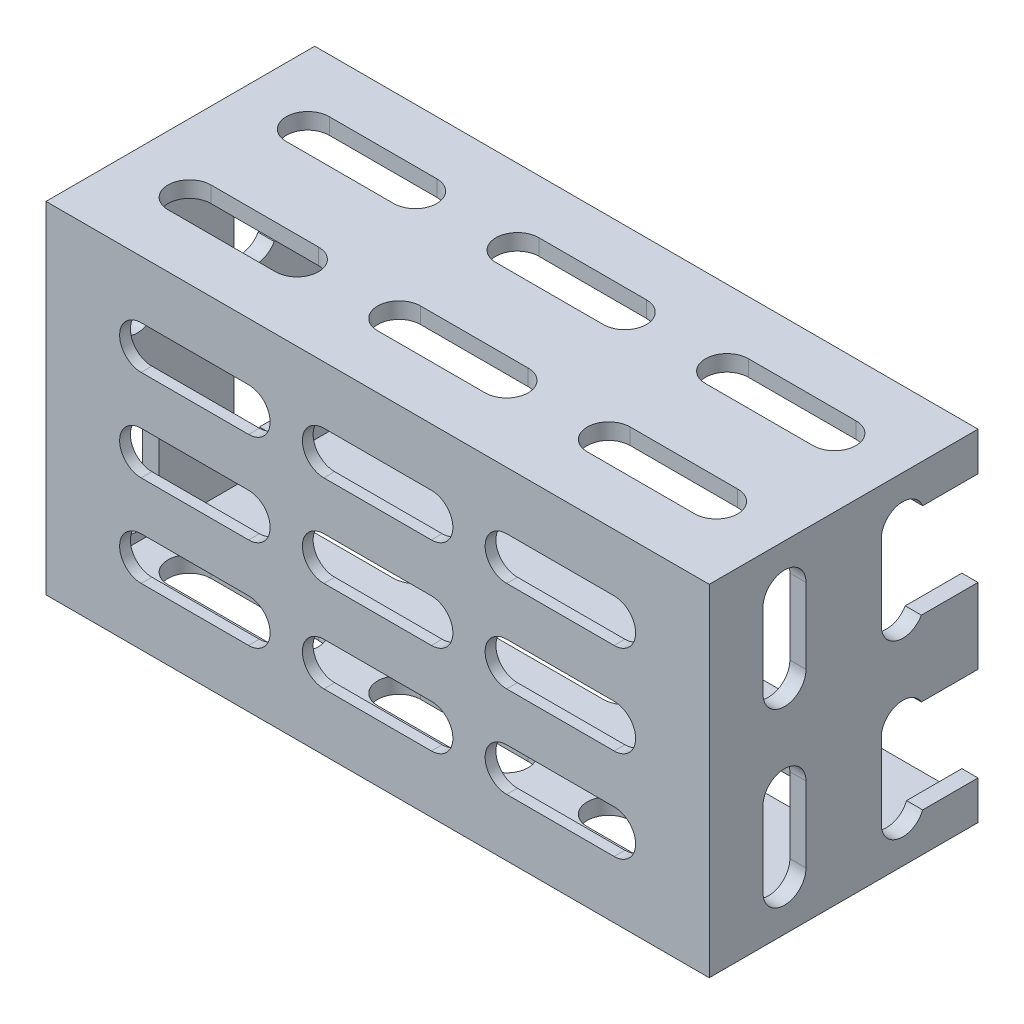
SolidWorks part; units mm, degrees
ref_plane "Front Plane" through (0, 0, 0) normal (0, 0, 1) x (1, 0, 0)
ref_plane "Top Plane" through (0, 0, 0) normal (0, 1, 0) x (1, 0, 0)
ref_plane "Right Plane" through (0, 0, 0) normal (1, 0, 0) x (0, 0, -1)
sketch "Sketch1" plane through (0, 0, 0) normal (0, 0, 1) x (1, 0, 0)
  line L4 (29.35, -14.35) -> (-29.35, -14.35)
  line L5 (29.25, -14.25) -> (-29.25, -14.25) construction
  line L6 (29.25, -14.25) -> (29.25, 14.25) construction
  line L7 (29.25, 14.25) -> (-29.25, 14.25) construction
  line L16 (-29.25, -14.25) -> (-29.25, 14.25) construction
  line L17 (-29.35, -14.35) -> (-29.35, 14.35)
  line L18 (29.35, 14.35) -> (-29.35, 14.35)
  line L19 (29.35, -14.35) -> (29.35, 14.35)
  line L20 (-30.85, -15.85) -> (-30.85, 15.85)
  line L21 (30.85, 15.85) -> (-30.85, 15.85)
  line L22 (30.85, -15.85) -> (30.85, 15.85)
  line L23 (30.85, -15.85) -> (-30.85, -15.85)
  dimension "D1" = 0.1
  dimension "D2" = 1.5
extrude "Boss-Extrude1" add sketch "Sketch1" along normal blind 19
sketch "Sketch2" plane through (0, 0, 19) normal (0, 0, 1) x (1, 0, 0)
  line L4 (-30.85, -15.85) -> (30.85, -15.85)
  line L5 (-30.85, -15.85) -> (30.85, -15.85)
  line L6 (-30.85, 15.85) -> (-30.85, -15.85)
  line L7 (30.85, 15.85) -> (-30.85, 15.85)
  line L10 (-30.85, 15.85) -> (-30.85, -15.85)
  line L11 (30.85, 15.85) -> (-30.85, 15.85)
  line L12 (30.85, -15.85) -> (30.85, 15.85)
  line L13 (30.85, -15.85) -> (30.85, 15.85)
  dimension "D1" = 0
extrude "Boss-Extrude2" add sketch "Sketch2" along normal blind 1
sketch "Sketch3" plane through (0, 0, 0) normal (0, 0, -1) x (-1, 0, 0)
  line L1 (29.35, -14.35) -> (-29.35, -14.35) construction
  line L4 (-30.85, -15.85) -> (30.85, -15.85)
  line L5 (30.85, 15.85) -> (-30.85, 15.85)
  line L6 (30.85, -15.85) -> (30.85, 15.85)
  line L7 (-30.85, -15.85) -> (30.85, -15.85)
  line L9 (30.85, 15.85) -> (9, 15.85)
  line L10 (30.85, -15.85) -> (30.85, 15.85)
  line L14 (29.35, 14.35) -> (29.35, -14.35) construction
  line L20 (-29.35, 14.35) -> (29.35, 14.35) construction
  line L21 (-29.35, -14.35) -> (-29.35, 14.35) construction
  line L22 (29.35, -14.35) -> (-29.35, -14.35)
  line L23 (29.35, 14.35) -> (29.35, -14.35)
  line L24 (-30.85, 15.85) -> (-30.85, -15.85)
  line L25 (-30.85, 15.85) -> (-30.85, -15.85)
  line L26 (-29.35, 14.35) -> (-9, 14.35)
  line L27 (-29.35, -14.35) -> (-29.35, 14.35)
  line L30 (-9, 15.85) -> (-30.85, 15.85)
  line L31 (9, 14.35) -> (29.35, 14.35)
  line L32 (-9, 15.85) -> (9, 15.85)
  line L33 (9, 14.35) -> (-9, 14.35)
  dimension "D1" = 0
extrude "Boss-Extrude3" add sketch "Sketch3" along normal up to surface (5 mm away)
sketch "Sketch8" plane through (0, 0, 19) normal (0, 0, -1) x (-1, 0, 0)
  line L0 (12, 6.5) -> (22, 6.5) construction
  line L1 (12, -2) -> (22, -2) construction
  line L2 (12, -10.5) -> (22, -10.5) construction
  line L3 (-5, -10.5) -> (5, -10.5) construction
  line L4 (-22, -10.5) -> (-12, -10.5) construction
  line L5 (-22, -2) -> (-12, -2) construction
  line L6 (-5, 6.5) -> (5, 6.5) construction
  line L7 (-22, 6.5) -> (-12, 6.5) construction
  line L8 (12, 6.5) -> (22, 6.5)
  line L9 (12, -2) -> (22, -2)
  line L10 (12, -10.5) -> (22, -10.5)
  line L11 (-5, -10.5) -> (5, -10.5)
  line L12 (-22, -10.5) -> (-12, -10.5)
  line L13 (-22, -2) -> (-12, -2)
  line L14 (-5, 6.5) -> (5, 6.5)
  line L15 (-22, 6.5) -> (-12, 6.5)
  line L16 (22, -6.5) -> (12, -6.5) construction
  line L17 (5, -6.5) -> (-5, -6.5) construction
  line L18 (-12, -6.5) -> (-22, -6.5) construction
  line L19 (22, 2) -> (12, 2) construction
  line L20 (-5, -2) -> (5, -2) construction
  line L21 (5, 2) -> (-5, 2) construction
  line L22 (-12, 2) -> (-22, 2) construction
  line L23 (22, 10.5) -> (12, 10.5) construction
  line L24 (5, 10.5) -> (-5, 10.5) construction
  line L25 (-12, 10.5) -> (-22, 10.5) construction
  line L26 (22, -6.5) -> (12, -6.5)
  line L27 (5, -6.5) -> (-5, -6.5)
  line L28 (-12, -6.5) -> (-22, -6.5)
  line L29 (22, 2) -> (12, 2)
  line L30 (-5, -2) -> (5, -2)
  line L31 (5, 2) -> (-5, 2)
  line L32 (-12, 2) -> (-22, 2)
  line L33 (22, 10.5) -> (12, 10.5)
  line L34 (5, 10.5) -> (-5, 10.5)
  line L35 (-12, 10.5) -> (-22, 10.5)
  arc A0 (22, -10.5) -> (22, -6.5) centre (22, -8.5) ccw construction
  arc A1 (12, -6.5) -> (12, -10.5) centre (12, -8.5) ccw construction
  arc A2 (5, -10.5) -> (5, -6.5) centre (5, -8.5) ccw construction
  arc A3 (-5, -6.5) -> (-5, -10.5) centre (-5, -8.5) ccw construction
  arc A4 (-12, -10.5) -> (-12, -6.5) centre (-12, -8.5) ccw construction
  arc A5 (-22, -6.5) -> (-22, -10.5) centre (-22, -8.5) ccw construction
  arc A6 (22, -2) -> (22, 2) centre (22, 0) ccw construction
  arc A7 (12, 2) -> (12, -2) centre (12, 0) ccw construction
  arc A8 (-5, 2) -> (-5, -2) centre (-5, 0) ccw construction
  arc A9 (5, -2) -> (5, 2) centre (5, 0) ccw construction
  arc A10 (-12, -2) -> (-12, 2) centre (-12, 0) ccw construction
  arc A11 (-22, 2) -> (-22, -2) centre (-22, 0) ccw construction
  arc A12 (22, 6.5) -> (22, 10.5) centre (22, 8.5) ccw construction
  arc A13 (12, 10.5) -> (12, 6.5) centre (12, 8.5) ccw construction
  arc A14 (-5, 10.5) -> (-5, 6.5) centre (-5, 8.5) ccw construction
  arc A15 (-12, 6.5) -> (-12, 10.5) centre (-12, 8.5) ccw construction
  arc A16 (-22, 10.5) -> (-22, 6.5) centre (-22, 8.5) ccw construction
  arc A17 (22, -10.5) -> (22, -6.5) centre (22, -8.5) ccw
  arc A18 (12, -6.5) -> (12, -10.5) centre (12, -8.5) ccw
  arc A19 (5, -10.5) -> (5, -6.5) centre (5, -8.5) ccw
  arc A20 (-5, -6.5) -> (-5, -10.5) centre (-5, -8.5) ccw
  arc A21 (-12, -10.5) -> (-12, -6.5) centre (-12, -8.5) ccw
  arc A22 (-22, -6.5) -> (-22, -10.5) centre (-22, -8.5) ccw
  arc A23 (22, -2) -> (22, 2) centre (22, 0) ccw
  arc A24 (12, 2) -> (12, -2) centre (12, 0) ccw
  arc A25 (-5, 2) -> (-5, -2) centre (-5, 0) ccw
  arc A26 (5, -2) -> (5, 2) centre (5, 0) ccw
  arc A27 (-12, -2) -> (-12, 2) centre (-12, 0) ccw
  arc A28 (-22, 2) -> (-22, -2) centre (-22, 0) ccw
  arc A29 (22, 6.5) -> (22, 10.5) centre (22, 8.5) ccw
  arc A30 (12, 10.5) -> (12, 6.5) centre (12, 8.5) ccw
  arc A31 (-5, 10.5) -> (-5, 6.5) centre (-5, 8.5) ccw
  arc A32 (-12, 6.5) -> (-12, 10.5) centre (-12, 8.5) ccw
  arc A33 (-22, 10.5) -> (-22, 6.5) centre (-22, 8.5) ccw
  arc A34 (5, 6.5) -> (5, 10.5) centre (5, 8.5) ccw construction
  arc A35 (5, 6.5) -> (5, 10.5) centre (5, 8.5) ccw
extrude "Cut-Extrude4" cut sketch "Sketch8" against normal through all
sketch "Sketch5" plane through (-15, 15.85, 0) normal (0, -1, 0) x (1, 0, 0)
  line L0 (-9.5, 2) -> (0.5, 2) construction
  line L1 (-9.5, 4) -> (0.5, 4)
  line L2 (-9.5, 0) -> (0.5, 0)
  line L3 (-15.85, 7.5) -> (45.85, 7.5) construction
  line L4 (45.85, -5) -> (-15.85, -5) construction
  line L5 (-15.85, 20) -> (45.85, 20) construction
  line L6 (15, -5) -> (15, 20) construction
  line L7 (45.85, 13) -> (-15.85, 13) construction
  line L8 (-15.85, 20) -> (-15.85, -5) construction
  line L9 (-4.5, 20) -> (-4.5, -5) construction
  line L10 (45.85, 2) -> (-15.85, 2) construction
  line L11 (34.5, 20) -> (34.5, -5) construction
  line L13 (10, 0) -> (20, 0)
  line L14 (10, 4) -> (20, 4)
  line L15 (10, 2) -> (20, 2) construction
  line L16 (29.5, 0) -> (39.5, 0)
  line L17 (29.5, 4) -> (39.5, 4)
  line L18 (29.5, 2) -> (39.5, 2) construction
  line L19 (10, 11) -> (20, 11)
  line L20 (10, 15) -> (20, 15)
  line L21 (10, 13) -> (20, 13) construction
  line L22 (29.5, 11) -> (39.5, 11)
  line L23 (29.5, 15) -> (39.5, 15)
  line L24 (29.5, 13) -> (39.5, 13) construction
  line L25 (-9.5, 11) -> (0.5, 11)
  line L26 (-9.5, 15) -> (0.5, 15)
  line L27 (-9.5, 13) -> (0.5, 13) construction
  line L28 (45.85, 20) -> (45.85, -5) construction
  arc A0 (-9.5, 4) -> (-9.5, 0) centre (-9.5, 2) ccw
  arc A1 (0.5, 0) -> (0.5, 4) centre (0.5, 2) ccw
  arc A2 (10, 4) -> (10, 0) centre (10, 2) ccw
  arc A3 (20, 0) -> (20, 4) centre (20, 2) ccw
  arc A4 (29.5, 4) -> (29.5, 0) centre (29.5, 2) ccw
  arc A5 (39.5, 0) -> (39.5, 4) centre (39.5, 2) ccw
  arc A6 (10, 15) -> (10, 11) centre (10, 13) ccw
  arc A7 (20, 11) -> (20, 15) centre (20, 13) ccw
  arc A8 (29.5, 15) -> (29.5, 11) centre (29.5, 13) ccw
  arc A9 (39.5, 11) -> (39.5, 15) centre (39.5, 13) ccw
  arc A10 (-9.5, 15) -> (-9.5, 11) centre (-9.5, 13) ccw
  arc A11 (0.5, 11) -> (0.5, 15) centre (0.5, 13) ccw
  point P2 (-4.5, 2)
  point P15 (45.85, 7.5)
  point P29 (15, -5)
  point P31 (15, 2)
  point P38 (34.5, 2)
  point P45 (15, 13)
  point P52 (34.5, 13)
  point P59 (-4.5, 13)
  dimension "D1" = 10
  dimension "D2" = 4
  dimension "D3" = 39
  dimension "D4" = 11
  dimension "D5" = 3
  dimension "D6" = 2
extrude "Cut-Extrude2" cut sketch "Sketch5" along normal through all
sketch "Sketch7" plane through (30.85, -15, 0) normal (-1, 0, 0) x (0, 0, -1)
  line L0 (-13, -26.5) -> (-13, -19.5) construction
  line L1 (-15, -26.5) -> (-15, -19.5)
  line L2 (-11, -26.5) -> (-11, -19.5)
  line L3 (-20, -15) -> (5, -15) construction
  line L4 (-20, -30.85) -> (-20, 0.85) construction
  line L5 (5, 0.85) -> (5, -30.85) construction
  line L6 (-7.5, 0.85) -> (-7.5, -30.85) construction
  line L7 (-20, 0.85) -> (5, 0.85) construction
  line L8 (-20, -30.85) -> (5, -30.85) construction
  line L9 (-13, -30.85) -> (-13, 0.85) construction
  line L10 (-20, -7) -> (5, -7) construction
  line L11 (-20, -23) -> (5, -23) construction
  line L12 (-2, -30.85) -> (-2, 0.85) construction
  line L13 (0, -26.5) -> (0, -19.5)
  line L14 (-4, -26.5) -> (-4, -19.5)
  line L15 (-2, -26.5) -> (-2, -19.5) construction
  line L16 (0, -10.5) -> (0, -3.5)
  line L17 (-4, -10.5) -> (-4, -3.5)
  line L18 (-2, -10.5) -> (-2, -3.5) construction
  line L19 (-11, -10.5) -> (-11, -3.5)
  line L20 (-15, -10.5) -> (-15, -3.5)
  line L21 (-13, -10.5) -> (-13, -3.5) construction
  arc A0 (-15, -26.5) -> (-11, -26.5) centre (-13, -26.5) ccw
  arc A1 (-11, -19.5) -> (-15, -19.5) centre (-13, -19.5) ccw
  arc A2 (-4, -26.5) -> (0, -26.5) centre (-2, -26.5) ccw
  arc A3 (0, -19.5) -> (-4, -19.5) centre (-2, -19.5) ccw
  arc A4 (-4, -10.5) -> (0, -10.5) centre (-2, -10.5) ccw
  arc A5 (0, -3.5) -> (-4, -3.5) centre (-2, -3.5) ccw
  arc A6 (-15, -10.5) -> (-11, -10.5) centre (-13, -10.5) ccw
  arc A7 (-11, -3.5) -> (-15, -3.5) centre (-13, -3.5) ccw
  point P2 (-13, -23)
  point P16 (-20, -15)
  point P32 (-2, -23)
  point P39 (-2, -7)
  point P46 (-13, -7)
  dimension "D1" = 7
  dimension "D2" = 4
  dimension "D3" = 16
  dimension "D6" = 11
  dimension "D4" = 2
  dimension "D5" = 2
extrude "Cut-Extrude3" cut sketch "Sketch7" along normal through all
sketch "Sketch9" plane through (-30.85, 0, 0) normal (-1, 0, 0) x (0, 0, 1)
  line L0 (-5, 0) -> (20, 0) construction
  line L1 (-5, 3.5) -> (2, 3.5)
  line L2 (-5, 3.5) -> (-5, 12.25)
  line L3 (-5, 12.25) -> (2, 12.25)
  line L4 (2, 3.5) -> (2, 12.25)
  line L6 (-5, -15.85) -> (-5, 15.85) construction
  line L7 (20, 15.85) -> (20, -15.85) construction
  line L8 (2, -3.5) -> (2, -12.25)
  line L9 (-5, -12.25) -> (2, -12.25)
  line L10 (-5, -3.5) -> (-5, -12.25)
  line L11 (-5, -3.5) -> (2, -3.5)
  arc A0 (4, 11.5) -> (0, 11.5) centre (2, 11.5) ccw construction
  point P22 (2, 13.5)
extrude "Cut-Extrude5" cut sketch "Sketch9" against normal through all
